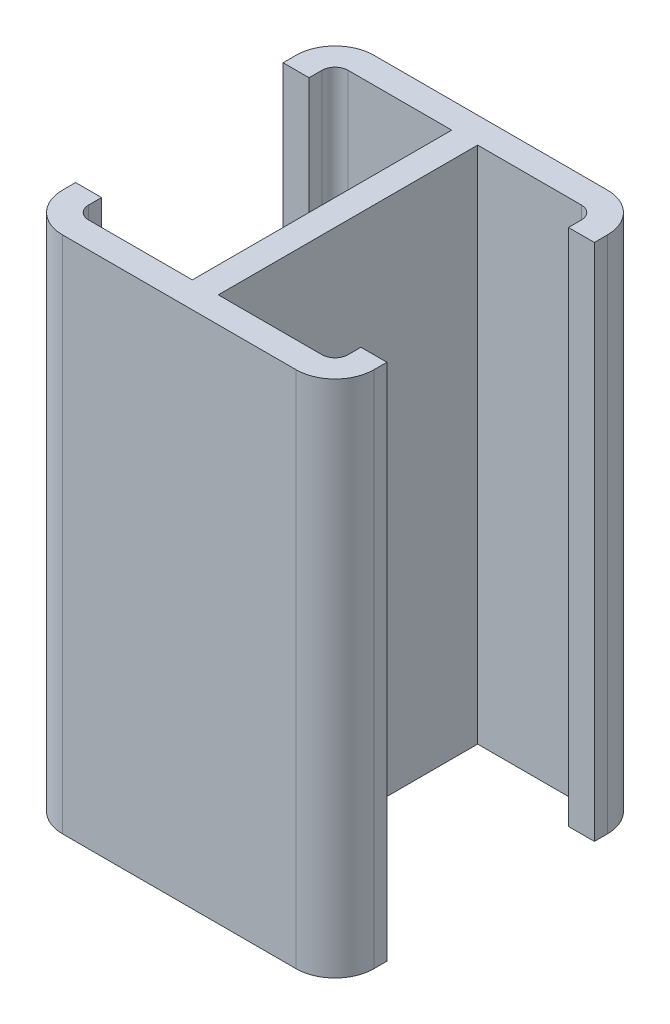
SolidWorks part; units mm, degrees
ref_plane "正面" through (0, 0, 0) normal (0, 0, 1) x (1, 0, 0)
ref_plane "平面" through (0, 0, 0) normal (0, 1, 0) x (1, 0, 0)
ref_plane "右側面" through (0, 0, 0) normal (1, 0, 0) x (0, 0, -1)
sketch "ｽｹｯﾁ1" plane through (0, 0, 0) normal (0, 1, 0) x (1, 0, 0)
  line L0 (0, 0) -> (0, -60)
  line L1 (0, -60) -> (45, -60)
  line L2 (60, -45) -> (60, -40)
  line L3 (60, -40) -> (50, -40)
  line L4 (50, -40) -> (50, -45)
  line L5 (45, -50) -> (5, -50)
  line L6 (5, -50) -> (5, 0)
  line L7 (5, 0) -> (0, 0)
  arc A0 (60, -45) -> (45, -60) centre (45, -45) cw
  arc A1 (50, -45) -> (45, -50) centre (45, -45) cw
  point P11 (60, -60)
  point P14 (50, -50)
  dimension "D7" = 15
  dimension "D8" = 5
  dimension "D1" = 60
  dimension "D2" = 60
  dimension "D3" = 20
  dimension "D4" = 10
  dimension "D5" = 10
  dimension "D6" = 5
extrude "ﾎﾞｽ - 押し出し1" add sketch "ｽｹｯﾁ1" along normal blind 200
mirror "ﾐﾗｰ1" about plane through (0, 200, 0) normal (1, 0, 0) of bodies 101
mirror "ﾐﾗｰ2" about plane through (5, 200, 0) normal (0, 0, 1) of bodies 104
equation "\"C\"= 20.0"
equation "\"D3@ｽｹｯﾁ1\"=\"C\""
equation "\"B\"= 10.0"
equation "\"D4@ｽｹｯﾁ1\"=\"B\""
equation "\"D5@ｽｹｯﾁ1\"=\"B\""
equation "\"A\"= 10.0"
equation "\"D6@ｽｹｯﾁ1\"=\"A\"/2"
equation "\"D8@ｽｹｯﾁ1\"= \"B\"/2"
equation "\"D7@ｽｹｯﾁ1\"= \"B\"/2*3"
